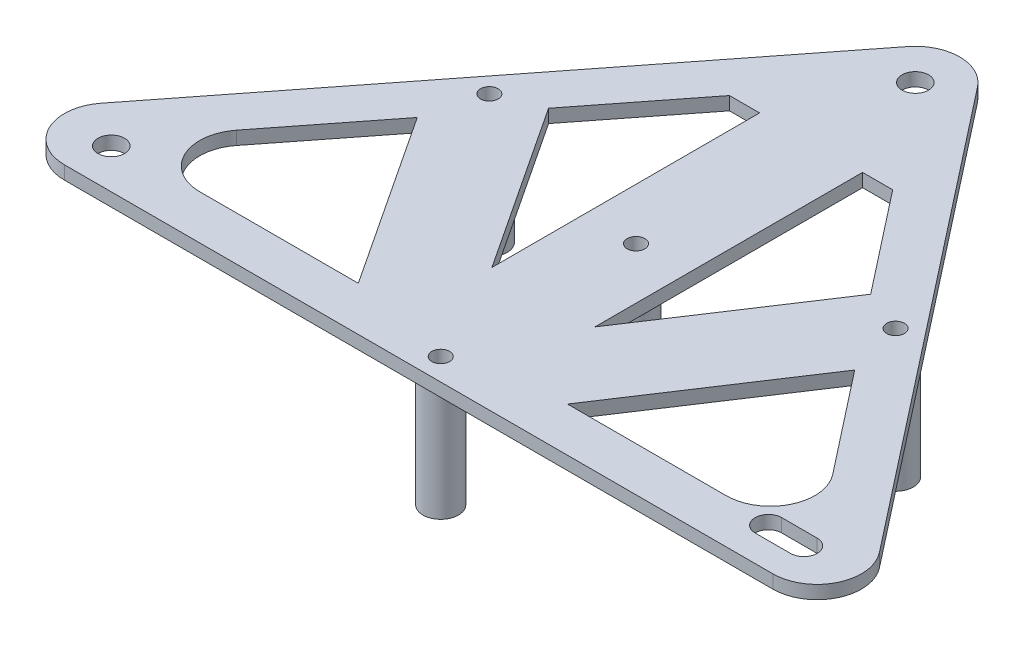
SolidWorks part; units mm, degrees
ref_plane "Front Plane" through (0, 0, 0) normal (0, 0, 1) x (1, 0, 0)
ref_plane "Top Plane" through (0, 0, 0) normal (0, 1, 0) x (1, 0, 0)
ref_plane "Right Plane" through (0, 0, 0) normal (1, 0, 0) x (0, 0, -1)
sketch "Sketch1" plane through (0, 0, 0) normal (0, 1, 0) x (1, 0, 0)
  line L1 (11.0372, 17.1903) -> (28.9594, 40.0777)
  line L2 (166.098, 7.1903) -> (86.1751, 109.2554)
  line L5 (-9.4945, 7.1903) -> (70.4284, 109.2554)
  line L6 (-1.6212, -8.975) -> (158.2247, -8.975)
  line L8 (18.9105, 1.025) -> (54.7068, 1.025)
  line L9 (-1.6212, 1.025) -> (158.2247, 1.025) construction
  line L10 (156.2441, 0) -> (148.2441, 0) construction
  line L13 (158.2247, 1.025) -> (78.3018, 103.0901) construction
  line L14 (-1.6212, 1.025) -> (78.3018, 103.0901) construction
  line L17 (78.3018, 85.0301) -> (78.3018, -8.975)
  line L18 (89.9189, 19.1924) -> (114.6386, 56.6863)
  line L19 (101.8967, 1.025) -> (127.6442, 40.0777)
  line L20 (137.693, 1.025) -> (101.8967, 1.025)
  line L21 (89.9189, 79.5737) -> (89.9189, 19.1924)
  line L22 (66.6846, 79.5737) -> (66.6846, 19.1924)
  line L23 (89.9189, 79.5737) -> (96.7165, 79.5737)
  line L24 (145.5663, 17.1903) -> (127.6442, 40.0777)
  line L25 (41.9649, 56.6863) -> (59.887, 79.5737)
  line L26 (66.6846, 79.5737) -> (59.887, 79.5737)
  line L27 (11.0372, 17.1903) -> (59.887, 79.5737) construction
  line L28 (66.6846, 79.5737) -> (66.6846, 1.025) construction
  line L32 (66.6846, 79.5737) -> (66.6846, 66.3647)
  line L33 (66.6846, 19.1924) -> (41.9649, 56.6863)
  line L34 (54.7068, 1.025) -> (28.9594, 40.0777)
  line L35 (18.9105, 1.025) -> (66.6846, 1.025) construction
  line L36 (60.6846, 70.8603) -> (60.6846, 70.8603)
  line L37 (114.6386, 56.6863) -> (96.7165, 79.5737)
  line L38 (156.2441, -3) -> (148.2441, -3)
  line L39 (156.2441, 3) -> (148.2441, 3)
  line L40 (60.6846, 70.8603) -> (60.6846, 7.025) construction
  line L48 (15.7612, 13.4911) -> (60.6846, 70.8603) construction
  line L49 (18.9105, 7.025) -> (60.6846, 7.025) construction
  arc A3 (-9.4945, 7.1903) -> (-1.6212, -8.975) centre (-1.6212, 1.025) ccw
  arc A4 (166.098, 7.1903) -> (158.2247, -8.975) centre (158.2247, 1.025) cw
  arc A5 (86.1751, 109.2554) -> (70.4284, 109.2554) centre (78.3018, 103.0901) ccw
  circle A6 centre (78.3018, 103.0901) radius 3
  circle A7 centre (156.2441, 0) radius 3
  circle A8 centre (0, 0) radius 3
  arc A15 (158.2247, 1.025) -> (158.2247, 1.025) centre (158.2247, 1.025) cw construction
  arc A17 (78.3018, 103.0901) -> (78.3018, 103.0901) centre (78.3018, 103.0901) ccw construction
  arc A18 (18.9105, 1.025) -> (11.0372, 17.1903) centre (18.9105, 11.025) cw
  arc A19 (-1.6212, 1.025) -> (-1.6212, 1.025) centre (-1.6212, 1.025) ccw construction
  arc A21 (18.9105, 7.025) -> (15.7612, 13.4911) centre (18.9105, 11.025) cw construction
  arc A22 (137.693, 1.025) -> (145.5663, 17.1903) centre (137.693, 11.025) ccw
  circle A23 centre (32.48, 52.8155) radius 2
  circle A32 centre (78.3018, -3.975) radius 2
  circle A34 centre (78.3018, 40.0777) radius 2
  circle A37 centre (124.1235, 52.8155) radius 2
  arc A38 (156.2441, -3) -> (156.2441, 3) centre (156.2441, 0) ccw
  arc A39 (148.2441, 3) -> (148.2441, -3) centre (148.2441, 0) ccw
  circle A40 centre (32.48, 52.8155) radius 4
  circle A42 centre (124.1235, 52.8155) radius 4
  circle A43 centre (78.3018, 40.0777) radius 4
  circle A44 centre (78.3018, -3.975) radius 4
  point P23 (152.2441, 0)
  dimension "D1" = 10
  dimension "D2" = 10
  dimension "D3" = 4
extrude "Boss-Extrude1" add sketch "Sketch1" along normal blind 3 contours A44 L6 A4 L2 A5 L5 A3 A43 A42 A40 A39 L39 A7 L38 L8 A18 L1 L34 L37 L18 L21 L23 L22 L33 L25 L26 A6 A8 A22 L20 L19 L24 | A40 A23 | L17 A43 A34 | L17 A43 A34 | L17 A44 A32 | L17 A44 A32 | A42 A37 region at (74.3912, 0, -40.0777) region at (78.3912, 0, -37.0777) region at (74.3912, 0, 3.975) region at (78.3912, 0, 6.975) region at (77.9065, 0, -35.021) region at (28.5931, 0, -52.8155) region at (120.2367, 0, -52.8155)
extrude "Boss-Extrude2" add sketch "Sketch1<4>" against normal blind 26 contours A40 | A43 | A42 | A44 | A23 | A34 | A37 | A32
sketch "Sketch1<4>" plane through (0, 0, 0) normal (0, 1, 0) x (1, 0, 0) same geometry as "Sketch1"
